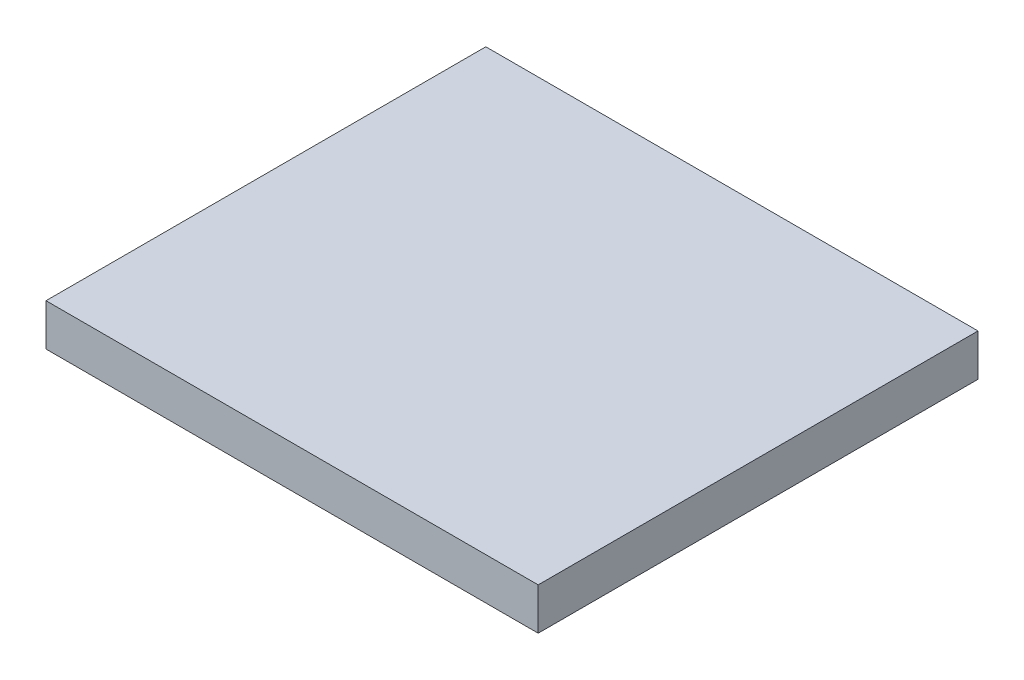
SolidWorks part; units mm, degrees
ref_plane "Front Plane" through (0, 0, 0) normal (0, 0, 1) x (1, 0, 0)
ref_plane "Top Plane" through (0, 0, 0) normal (0, 1, 0) x (1, 0, 0)
ref_plane "Right Plane" through (0, 0, 0) normal (1, 0, 0) x (0, 0, -1)
sketch "Sketch1" plane through (0, 0, 0) normal (0, 1, 0) x (1, 0, 0)
  line L1 (0, 0) -> (141, 0)
  line L2 (0, 0) -> (0, 126)
  line L3 (0, 126) -> (141, 126)
  line L4 (141, 0) -> (141, 126)
  line L5 (5, 5) -> (136, 5)
  line L6 (5, 5) -> (5, 121)
  line L7 (5, 121) -> (136, 121)
  line L8 (136, 5) -> (136, 121)
  dimension "D1" = 5
  dimension "D2" = 5
  dimension "D3" = 5
  dimension "D4" = 5
  dimension "D5" = 141
  dimension "D6" = 126
extrude "Boss-Extrude1" add sketch "Sketch1" against normal blind 10
extrude "Boss-Extrude2" add sketch "Sketch1<2>" along normal blind 2 contours L1 L4 L3 L2 L8 L5 L6 L7 | L5 L8 L7 L6 region at (1.891, 0, -63) region at (70.5, 0, -63)
sketch "Sketch1<2>" plane through (0, 0, 0) normal (0, 1, 0) x (1, 0, 0) same geometry as "Sketch1"
